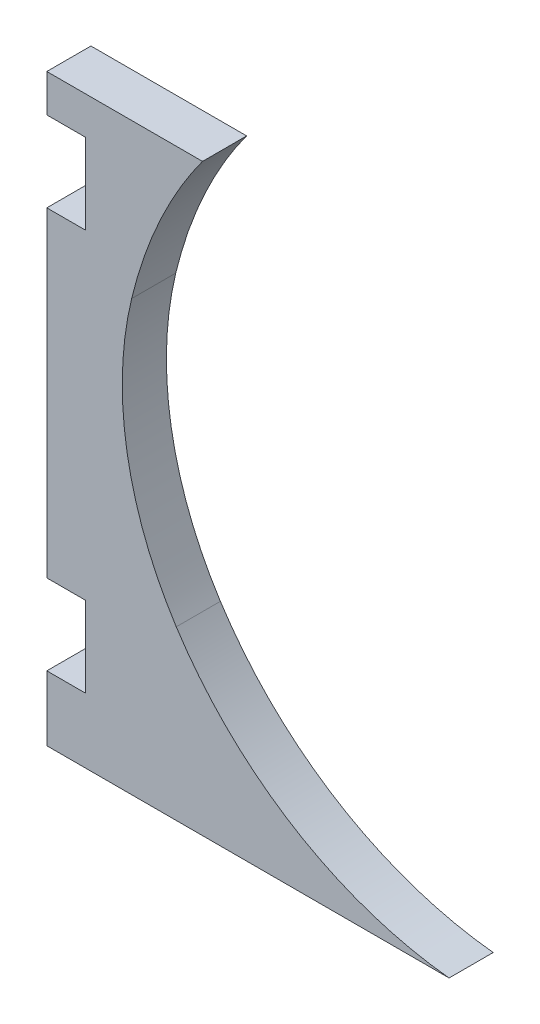
SolidWorks part; units mm, degrees
ref_plane "Front Plane" through (0, 0, 0) normal (0, 0, 1) x (1, 0, 0)
ref_plane "Top Plane" through (0, 0, 0) normal (0, 1, 0) x (1, 0, 0)
ref_plane "Right Plane" through (0, 0, 0) normal (1, 0, 0) x (0, 0, -1)
sketch "Sketch1" plane through (0, 0, 0) normal (0, 0, 1) x (1, 0, 0)
  line L1 (-70, 112.5) -> (70, 112.5)
  line L2 (-70, 112.5) -> (-70, -112.5)
  line L3 (-70, -112.5) -> (70, -112.5)
  line L4 (70, 112.5) -> (70, -112.5)
  line L5 (-70, 112.5) -> (70, -112.5) construction
  line L6 (-70, -112.5) -> (70, 112.5) construction
  point P0 (0, 0)
  dimension "D1" = 140
  dimension "D2" = 225
extrude "Boss-Extrude1" add sketch "Sketch1" along normal blind 17
sketch "Sketch2" plane through (0, 0, 17) normal (0, 0, 1) x (1, 0, 0)
  line L0 (-70, -112.5) -> (70, -112.5) construction
  line L1 (-70, 112.5) -> (-70, -112.5) construction
  line L3 (-35, 112.5) -> (70, 112.5)
  line L4 (70, 112.5) -> (70, -112.5)
  line L5 (70, 112.5) -> (-70, 112.5) construction
  arc A0 (70, -112.5) -> (-57, 12.8292) centre (85, 29.7111) cw
  spline S1 degree 3 poles (-57, 12.8292) (-57.2309, 51.9086) (-43.4996, 87.4349) (-25, 112.5) knots 0 0 0 0 1 1 1 1
  spline S2 degree 1 poles (-57, 12.8292) (70, -112.5) knots 0 0 1 1
  line M1 (70, -112.5) -> (70, 112.5)
  line M2 (70, 112.5) -> (-70, 112.5)
  dimension "D1" = 143
  dimension "D8" = 45
  dimension "D2" = 13
  dimension "D4" = 225
  dimension "D5" = 15
  dimension "D6" = 142.2111
extrude "Cut-Extrude1" cut sketch "Sketch2" against normal through all contours S1 S2 M1 M2 | S2 A0 region at (17.8767, 24.1624, 17) region at (-2.3656, -58.8192, 17)
fillet "Fillet1" radius 130 1 edges at (-57, 12.8292, 8.5)
sketch "Sketch3" plane through (-70, 0, 0) normal (-1, 0, 0) x (0, 0, 1)
  line L1 (0, 112.5) -> (17, 112.5)
  line L2 (0, 112.5) -> (0, -112.5)
  line L3 (0, -112.5) -> (17, -112.5)
  line L4 (17, 112.5) -> (17, -112.5)
extrude "Boss-Extrude2" add sketch "Sketch3" along normal blind 15
sketch "Sketch4" plane through (0, 0, 0) normal (0, 0, -1) x (-1, 0, 0)
  line L0 (85, 112.5) -> (85, -112.5) construction
  line L1 (85, 98) -> (70, 98)
  line L2 (85, 98) -> (85, 67)
  line L3 (85, 67) -> (70, 67)
  line L4 (70, 98) -> (70, 67)
  line L5 (85, -112.5) -> (-70, -112.5) construction
  line L6 (85, -87.5) -> (70, -87.5)
  line L7 (85, -87.5) -> (85, -56.5)
  line L8 (85, -56.5) -> (70, -56.5)
  line L9 (70, -87.5) -> (70, -56.5)
  line L11 (25, 112.5) -> (85, 112.5) construction
  point P10 (77.5, -56.5)
  point P14 (85, 82.5)
  dimension "D1" = 31
  dimension "D2" = 15
  dimension "D3" = 31
  dimension "D4" = 15
  dimension "D5" = 25
  dimension "D6" = 30
extrude "Cut-Extrude3" cut sketch "Sketch4" against normal through all
